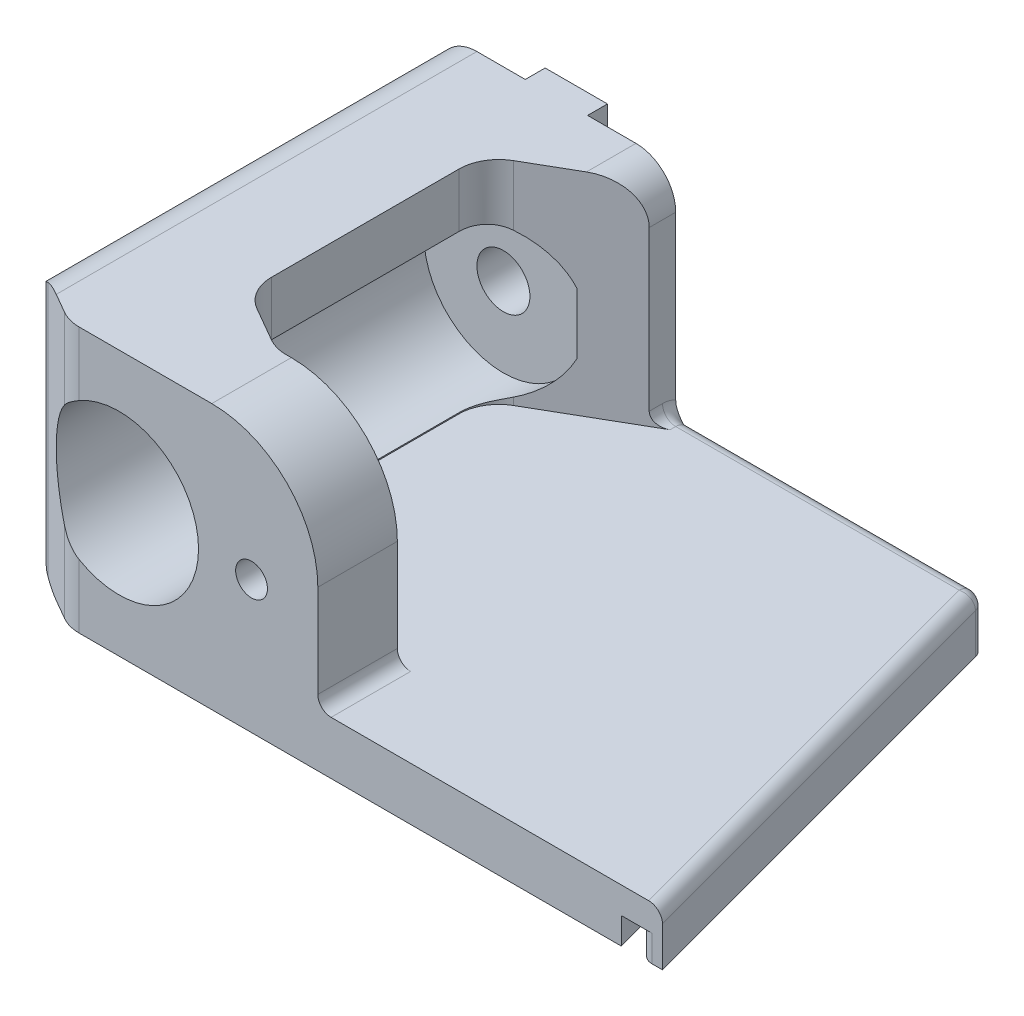
SolidWorks part; units mm, degrees
material "ABS"
ref_plane "Plan de face" through (0, 0, 0) normal (0, 0, 1) x (1, 0, 0)
ref_plane "Plan de dessus" through (0, 0, 0) normal (0, 1, 0) x (1, 0, 0)
ref_plane "Plan de droite" through (0, 0, 0) normal (1, 0, 0) x (0, 0, -1)
sketch "Esquisse1" plane through (0, 0, 0) normal (0, 1, 0) x (1, 0, 0)
  line L0 (2.35, 0) -> (9, 0)
  line L1 (-2.35, 1.5) -> (2.35, 1.5)
  line L2 (-2.35, 1.5) -> (-2.35, 0)
  line L3 (-2.35, 0) -> (2.35, 0) construction
  line L4 (2.35, 1.5) -> (2.35, 0)
  line L5 (-9, 0) -> (-2.35, 0)
  line L6 (-9, 0) -> (-9, -25)
  line L7 (1, -25) -> (-9, -25)
  line L8 (9, -2) -> (1, -6.6188)
  line L9 (1, -6.6188) -> (1, -25)
  line L10 (9, -2) -> (9, 0)
  dimension "D1" = 9
  dimension "D2" = 25
  dimension "D3" = 2
  dimension "D4" = 4.7
  dimension "D5" = 1.5
  dimension "D6" = 30
  dimension "D7" = 1
extrude "Boss.-Extru.1" add sketch "Esquisse1" along normal mid plane 20
sketch "Esquisse2" plane through (-1.3724, 0, 0) normal (0, 0, 1) x (1, 0, 0)
  circle A0 centre (1.3724, 0) radius 2
  dimension "D1" = 4
extrude "Enlèv. mat.-Extru.1" cut sketch "Esquisse2" against normal through all both and the other way through all
sketch "Esquisse3" plane through (0, 0, 0) normal (0, 0, 1) x (1, 0, 0)
  circle A0 centre (0, 0) radius 6
  dimension "D1" = 12
extrude "Enlèv. mat.-Extru.2" cut sketch "Esquisse3" along normal through all from offset 4
sketch "Esquisse5" plane through (-2.35, 0, 0) normal (-1, 0, 0) x (0, 0, 1)
  line L0 (-1.5, 10) -> (-1.5, -10) construction
  line L1 (-1.5, 2) -> (0, 2)
  line L2 (-1.5, 2) -> (-1.5, -2)
  line L3 (-1.5, -2) -> (0, -2)
  line L4 (0, 2) -> (0, -2)
  dimension "D1" = 4
extrude "Enlèv. mat.-Extru.3" [suppressed] cut sketch "Esquisse5" against normal through all
sketch "Esquisse6" plane through (0, 10, 0) normal (0, 1, 0) x (1, 0, 0)
  line L0 (-9, -18.453) -> (5.8038, -27)
  line L1 (-9, 0) -> (-9, -25) construction
  line L2 (5.8038, -27) -> (15, -27)
  line L3 (15, -27) -> (15, -33)
  line L4 (15, -33) -> (-3.8038, -33)
  line L5 (-3.8038, -33) -> (-9, -30)
  line L6 (-9, -30) -> (-9, -18.453)
  line L7 (9, 0) -> (2.35, 0) construction
  line L8 (-2.35, 0) -> (-9, 0) construction
  dimension "D1" = 6
  dimension "D2" = 33
  dimension "D3" = 15
  dimension "D4" = 30
  dimension "D5" = 30
  dimension "D6" = 10
extrude "Boss.-Extru.2" add sketch "Esquisse6" against normal up to surface (20 mm away) up to face at (0.2, -10, 5.5619)
sketch "Esquisse7" plane through (0, 0, 33) normal (0, 0, 1) x (1, 0, 0)
  circle A0 centre (10, 0) radius 1.2
  circle A1 centre (0, 0) radius 6 construction
  circle A2 centre (0, 0) radius 6
  dimension "D1" = 2.4
  dimension "D2" = 10
extrude "Enlèv. mat.-Extru.4" cut sketch "Esquisse7" against normal blind 20
fillet "Congé1" radius 3 14 edges at (-9, -10, 15) (-9, 10, 15) (9, -10, 1) (9, 10, 1) (15, -10, 30) (5.8038, 5.7608, 27) (5.8038, -5.7608, 27) (-3.8038, -7.3201, 33) (-3.8038, 7.3201, 33) (-9, 0, 30) (1, -7.958, 24.2265) (1, -7.958, 6.6188) (1, 7.958, 6.6188) (1, 7.958, 24.2265)
sketch "Esquisse8" plane through (0, -10, 0) normal (0, -1, 0) x (1, 0, 0)
  line L0 (12, 33) -> (-3, 33) construction
  line L1 (-2.35, 0) -> (32.1577, 0)
  line L2 (-2.35, 0) -> (-2.35, 33)
  line L3 (-2.35, 33) -> (41, 33)
  line L4 (32.1577, 0) -> (41, 33)
  dimension "D1" = 32.1577
  dimension "D2" = 75
  dimension "D3" = 41
extrude "Boss.-Extru.3" add sketch "Esquisse8" against normal blind 4
sketch "Esquisse9" plane through (0, -10, 0) normal (0, -1, 0) x (1, 0, 0)
  line L4 (-9, 0) -> (-9, 28.2679) construction
  line L5 (-9, 1.5) -> (29.4538, 1.5)
  line L9 (-9, 1.5) -> (-9, -1.5)
  line L10 (-9, -1.5) -> (30.2028, -1.5)
  line L12 (32.1577, 0) -> (41, 33) construction
  line L13 (39.4471, 33) -> (37.8942, 33)
  line L14 (39.4471, 33) -> (30.2028, -1.5)
  line L16 (37.8942, 33) -> (29.4538, 1.5)
  line L17 (32.1577, 0) -> (2.35, 0) construction
  line L18 (41, 33) -> (-3, 33) construction
  line L19 (2.35, -1.5) -> (-2.35, -1.5) construction
  dimension "D1" = 1.5
  dimension "D2" = 1.5
  dimension "D3" = 1.5
extrude "Enlèv. mat.-Extru.5" cut sketch "Esquisse9" against normal blind 2
fillet "Congé2" radius 1 6 edges at (15, -6, 30) (32.1577, -8, 0) (29.4538, -9, 1.5) (36.5788, -6, 16.5) (20.5788, -6, 0) (39.4471, -9, 33)
fillet "Congé3" radius 1 2 edges at (9, -6.2929, 0.2929) (9, -6, 1.5)
sketch "Esquisse10" plane through (0, 0, 33) normal (0, 0, 1) x (1, 0, 0)
  line L1 (12.75, 1.5877) -> (10, 3.1754)
  line L2 (10, 3.1754) -> (7.25, 1.5877)
  line L3 (7.25, 1.5877) -> (7.25, -1.5877)
  line L4 (7.25, -1.5877) -> (10, -3.1754)
  line L5 (10, -3.1754) -> (12.75, -1.5877)
  line L6 (12.75, -1.5877) -> (12.75, 1.5877)
  circle A0 centre (10, 0) radius 2.75 construction
  circle A1 centre (10, 0) radius 1.2 construction
  dimension "D1" = 5.5
extrude "Enlèv. mat.-Extru.6" cut sketch "Esquisse10" against normal blind 6 from offset 3 offset against normal yes
fillet "Congé4" radius 8 1 edges at (15, 10, 30)
